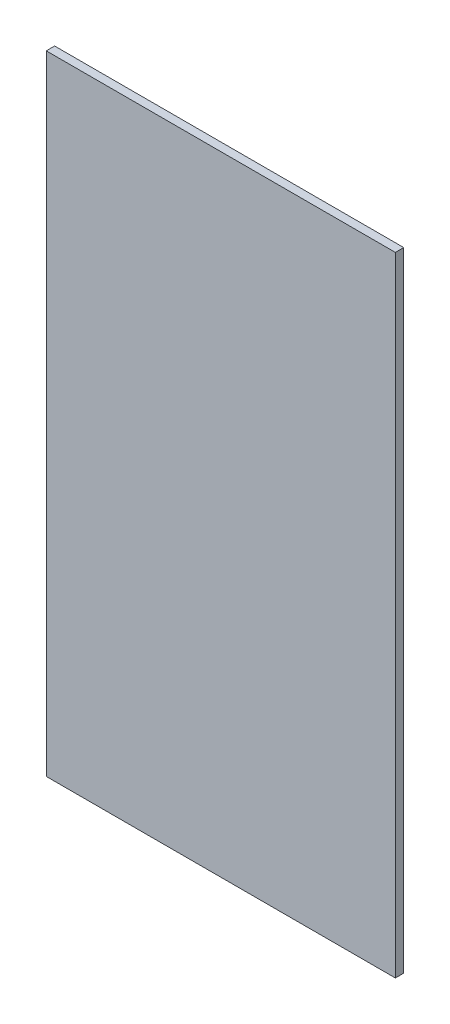
SolidWorks part; units mm, degrees
ref_plane "Ebene vorne" through (0, 0, 0) normal (0, 0, 1) x (1, 0, 0)
ref_plane "Ebene oben" through (0, 0, 0) normal (0, 1, 0) x (1, 0, 0)
ref_plane "Ebene rechts" through (0, 0, 0) normal (1, 0, 0) x (0, 0, -1)
sketch "DimensionsSketch" plane through (0, 0, 0) normal (0, 0, 1) x (1, 0, 0)
  line L1 (-125, -225) -> (125, -225)
  line L2 (-125, -225) -> (-125, 225)
  line L3 (-125, 225) -> (125, 225)
  line L4 (125, -225) -> (125, 225)
  line L5 (-125, -225) -> (125, 225) construction
  line L6 (-125, 225) -> (125, -225) construction
  point P0 (0, 0)
  dimension "D1" = 250
  dimension "D2" = 450
extrude "Dimensions" add sketch "DimensionsSketch" along normal mid plane 6
sketch "Sketch1" [suppressed] plane through (0, -225, 0) normal (0, -1, 0) x (1, 0, 0)
  line L4 (132, -20) -> (132, 20)
  line L5 (132, 20) -> (112, 0)
  line L6 (112, 0) -> (132, -20)
  line L7 (125, 0) -> (132, 0) construction
  line L8 (125, 3) -> (125, -3) construction
  dimension "D1" = 7
  dimension "D2" = 90
  dimension "D3" = 40
extrude "Boss-Extrude1" [suppressed] add sketch "Sketch1" against normal offset from surface (464 mm away) 7 from offset 7 up to face at (0, 225, 0) offset beyond the face yes
sketch "Sketch2" [suppressed] plane through (-125, 0, 0) normal (-1, 0, 0) x (0, 0, 1)
  line L0 (-20, -232) -> (20, -232)
  line L1 (20, -232) -> (0, -212)
  line L2 (0, -212) -> (-20, -232)
  dimension "D1" = 90
extrude "Boss-Extrude2" [suppressed] add sketch "Sketch2" against normal up to surface (264 mm away) from offset 7
mirror "Mirror1" [suppressed] about plane through (0, 0, 0) normal (1, 0, 0)
mirror "Mirror2" [suppressed] about plane through (0, 0, 0) normal (0, 1, 0)
